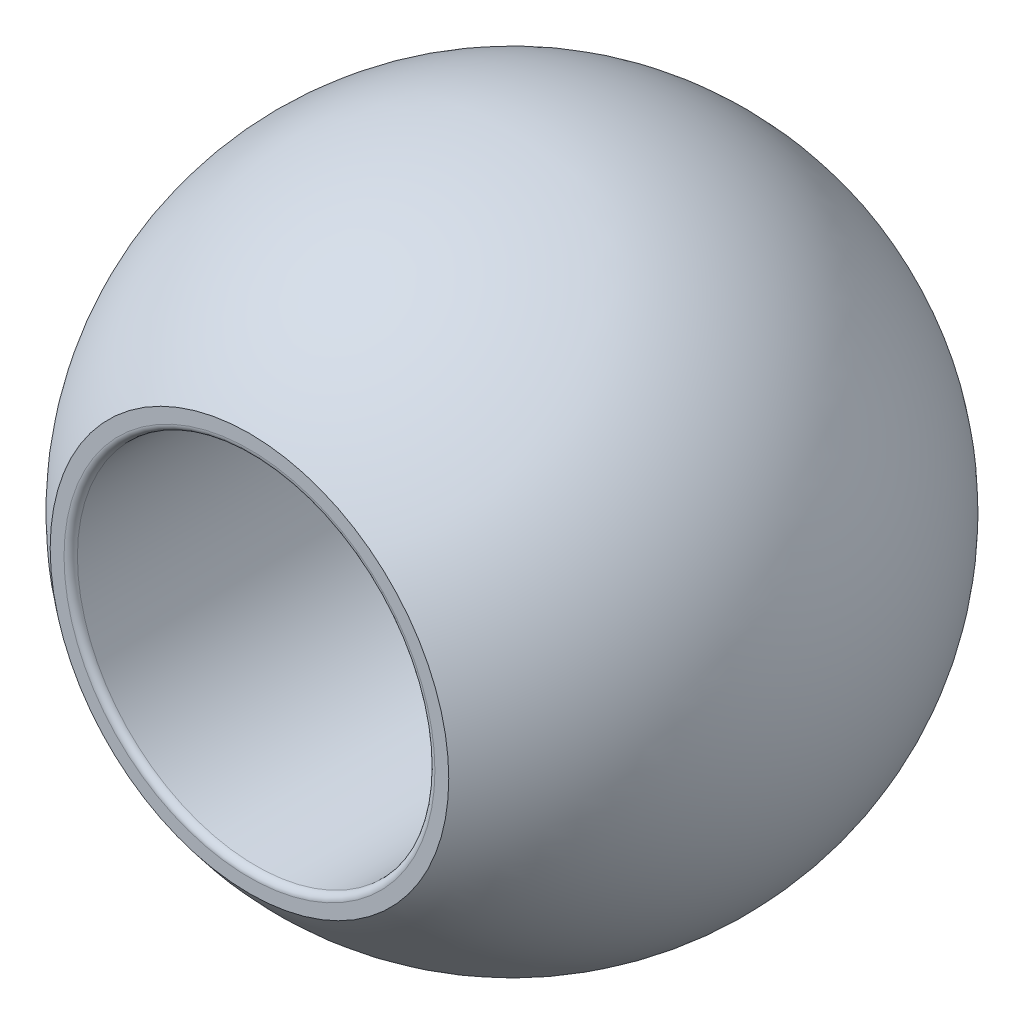
SolidWorks part; units mm, degrees
ref_plane "Plan de face" through (0, 0, 0) normal (0, 0, 1) x (1, 0, 0)
ref_plane "Plan de dessus" through (0, 0, 0) normal (0, 1, 0) x (1, 0, 0)
ref_plane "Plan de droite" through (0, 0, 0) normal (1, 0, 0) x (0, 0, -1)
sketch "Esquisse1" plane through (0, 0, 0) normal (0, 0, 1) x (1, 0, 0)
  line L0 (0, 4.0434) -> (0, -4.3851) construction
  line L1 (0, 2.95) -> (0, -2.95)
  arc A0 (0, 2.95) -> (0, -2.95) centre (0, 0) ccw
  dimension "D1" = 2.95
revolve "Révolution1" add sketch "Esquisse1" angle 360 about L0
sketch "Esquisse2" plane through (0, 0, 0) normal (0, 0, 1) x (1, 0, 0)
  circle A0 centre (0, 0) radius 1.6
  dimension "D1" = 3.2
extrude "Enlèv. mat.-Extru.1" cut sketch "Esquisse2" against normal up to next and the other way up to next
sketch "Esquisse3" plane through (0, 0, 0) normal (0, 1, 0) x (1, 0, 0)
  line L1 (1.9385, 2.3494) -> (-1.9385, 2.3494)
  line L2 (1.9385, 2.3494) -> (1.9385, 2.4994)
  line L3 (1.9385, 2.4994) -> (-1.9385, 2.4994)
  line L4 (-1.9385, 2.3494) -> (-1.9385, 2.4994)
  line L5 (1.9385, 2.3494) -> (-1.9385, 2.4994) construction
  line L6 (1.9385, 2.4994) -> (-1.9385, 2.3494) construction
  point P0 (0, 2.4244)
  dimension "D1" = 0.15
extrude "Enlèv. mat.-Extru.2" cut sketch "Esquisse3" against normal through all and the other way through all
fillet "Congé2" radius 0.06 1 edges at (1.6, 0, -2.3494)
mirror "Symétrie1" about plane through (0, 0, 0) normal (0, 0, 1) of "Congé2", "Enlèv. mat.-Extru.2"
